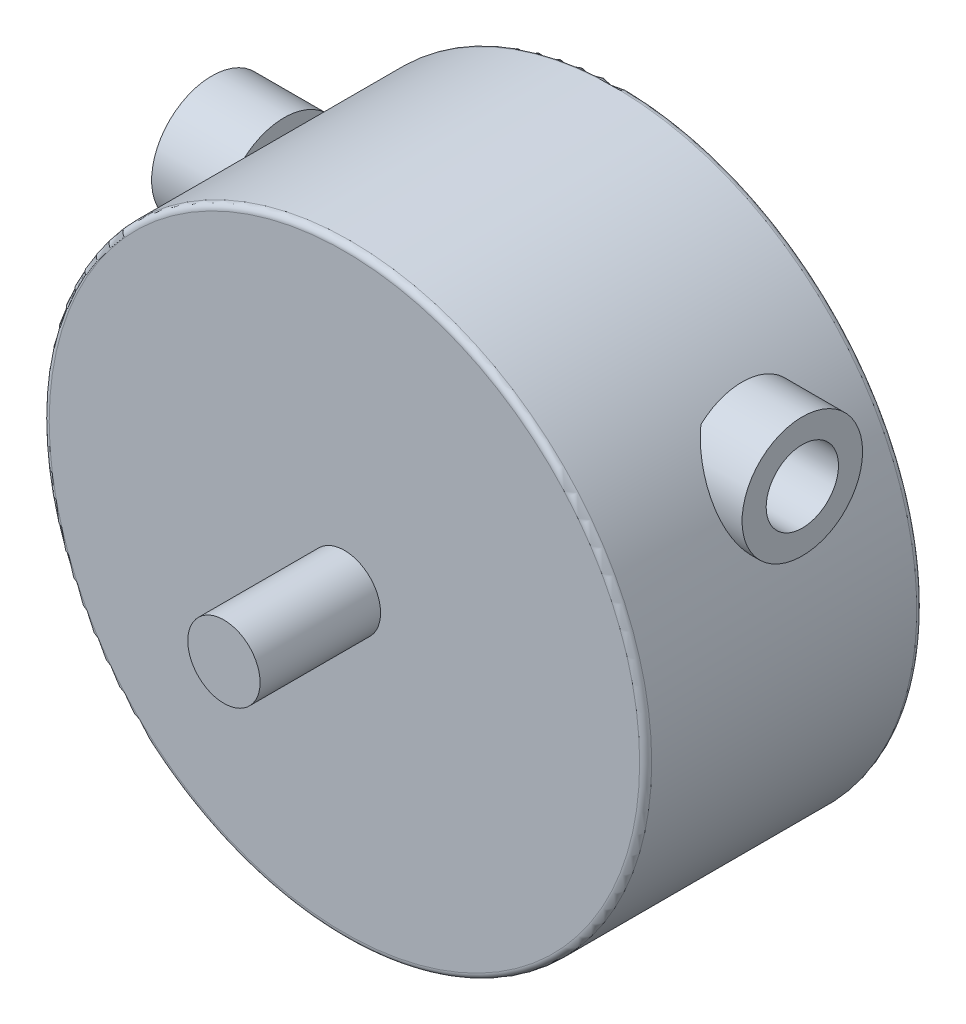
SolidWorks part; units mm, degrees
ref_plane "前视基准面" through (0, 0, 0) normal (0, 0, 1) x (1, 0, 0)
ref_plane "上视基准面" through (0, 0, 0) normal (0, 1, 0) x (1, 0, 0)
ref_plane "右视基准面" through (0, 0, 0) normal (1, 0, 0) x (0, 0, -1)
sketch "草图1" plane through (0, 0, 0) normal (0, 0, 1) x (1, 0, 0)
  circle A0 centre (0, 0) radius 25
extrude "凸台-拉伸1" add sketch "草图1" along normal blind 8
sketch "草图2" plane through (0, 0, 8) normal (0, 0, 1) x (1, 0, 0)
  circle A0 centre (0, 0) radius 3
extrude "凸台-拉伸2" add sketch "草图2" along normal blind 10
sketch "草图3" plane through (0, 0, 0) normal (0, 0, -1) x (-1, 0, 0)
  circle A0 centre (0, 0) radius 25
  circle A1 centre (0, 0) radius 20
extrude "凸台-拉伸3" add sketch "草图3" along normal blind 10
sketch "草图4" plane through (0, 0, 0) normal (0, 0, -1) x (-1, 0, 0)
  circle A0 centre (0, 0) radius 5
extrude "凸台-拉伸4" add sketch "草图4" along normal blind 2
sketch "草图5" plane through (0, 0, -2) normal (0, 0, -1) x (-1, 0, 0)
  circle A0 centre (0, 0) radius 2.5
extrude "凸台-拉伸5" add sketch "草图5" along normal blind 8
sketch "草图6" plane through (0, 0, -10) normal (0, 0, -1) x (-1, 0, 0)
  circle A0 centre (0, 0) radius 25
  circle A2 centre (0, 0) radius 5
extrude "凸台-拉伸6" add sketch "草图6" along normal blind 5
sketch "草图8" plane through (0, 0, 0) normal (1, 0, 0) x (0, 0, -1)
  circle A1 centre (6, 12.6) radius 3
extrude "切除-拉伸1" cut sketch "草图8" along normal through all and the other way through all
ref_plane "基准面4" through (-19, 0, 0) normal (1, 0, 0) x (0, 0, -1)
sketch "草图9" plane through (-19, 0, 0) normal (1, 0, 0) x (0, 0, -1)
  circle A0 centre (6, 12.6) radius 3
  circle A1 centre (6, 12.6) radius 5
extrude "凸台-拉伸7" add sketch "草图9" against normal through all
ref_plane "基准面5" through (19, 0, 0) normal (1, 0, 0) x (0, 0, -1)
sketch "草图10" plane through (19, 0, 0) normal (1, 0, 0) x (0, 0, -1)
  circle A1 centre (6, 12.6) radius 5
extrude "凸台-拉伸8" add sketch "草图10" along normal blind 5
sketch "草图11" plane through (24, 0, 0) normal (1, 0, 0) x (0, 0, -1)
  circle A0 centre (6, 12.6) radius 3
extrude "切除-拉伸2" cut sketch "草图11" against normal blind 5
fillet "圆角1" radius 0.5 2 edges at (25, 0, 8) (-25, 0, -15)
